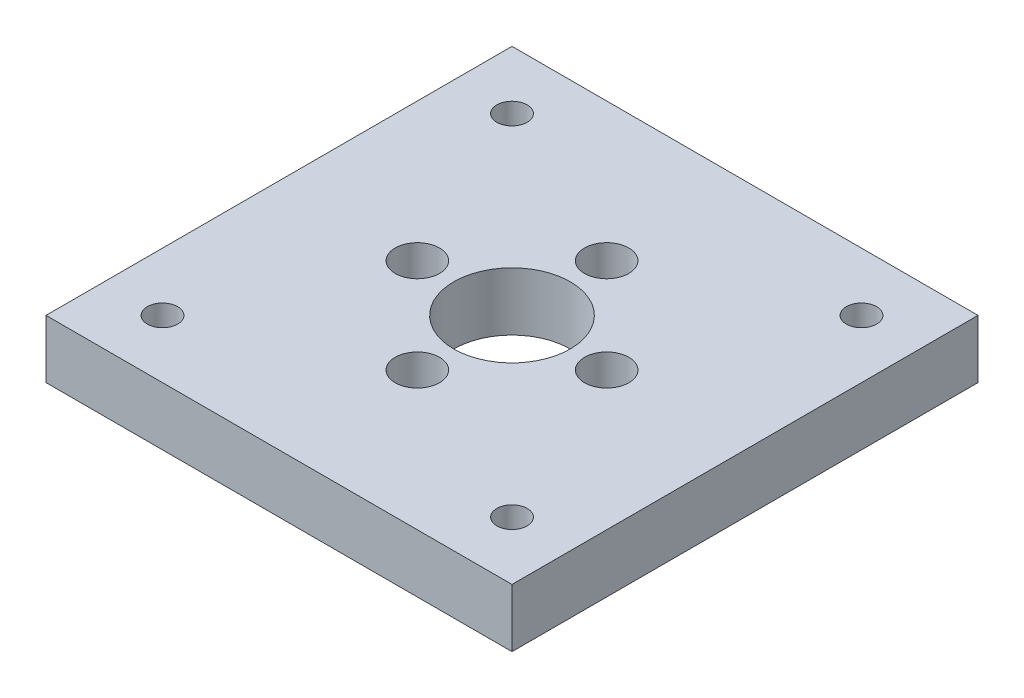
SolidWorks part; units mm, degrees
ref_plane "Front Plane" through (0, 0, 0) normal (0, 0, 1) x (1, 0, 0)
ref_plane "Top Plane" through (0, 0, 0) normal (0, 1, 0) x (1, 0, 0)
ref_plane "Right Plane" through (0, 0, 0) normal (1, 0, 0) x (0, 0, -1)
sketch "Sketch1" plane through (0, 0, 0) normal (0, 1, 0) x (1, 0, 0)
  line L0 (0, 24.4231) -> (0, -30.107) construction
  line L1 (-50.8, -50.8) -> (50.8, -50.8)
  line L2 (-50.8, -50.8) -> (-50.8, 50.8)
  line L3 (-50.8, 50.8) -> (50.8, 50.8)
  line L4 (50.8, -50.8) -> (50.8, 50.8)
  line L5 (-50.8, -50.8) -> (50.8, 50.8) construction
  line L6 (-50.8, 50.8) -> (50.8, -50.8) construction
  line L7 (-20.0713, 0) -> (21.8476, 0) construction
  circle A0 centre (-38.1, 38.1) radius 3.302
  circle A1 centre (-38.1, -38.1) radius 3.302
  circle A3 centre (38.1, -38.1) radius 3.302
  circle A4 centre (38.1, 38.1) radius 3.302
  circle A5 centre (0, 0) radius 12.7
  circle A6 centre (0, 20.6375) radius 4.826
  circle A7 centre (0, -20.6375) radius 4.826
  circle A8 centre (-20.6375, 0) radius 4.826
  circle A9 centre (20.6375, 0) radius 4.826
  point P0 (0, 0)
  dimension "D3" = 6.604
  dimension "D4" = 25.4
  dimension "D6" = 41.275
  dimension "D7" = 9.652
  dimension "D8" = 9.652
  dimension "D1" = 101.6
  dimension "D2" = 101.6
  dimension "D5" = 76.2
  dimension "D9" = 41.275
extrude "Boss-Extrude1" add sketch "Sketch1" along normal mid plane 12.7
